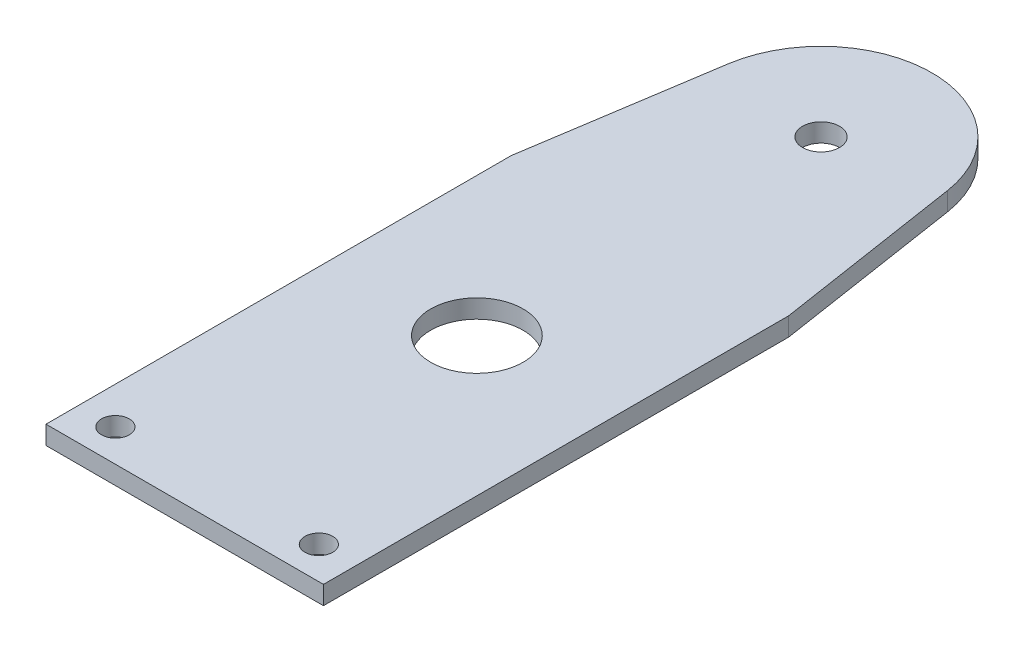
SolidWorks part; units mm, degrees
ref_plane "Спереди" through (0, 0, 0) normal (0, 0, 1) x (1, 0, 0)
ref_plane "Сверху" through (0, 0, 0) normal (0, 1, 0) x (1, 0, 0)
ref_plane "Справа" through (0, 0, 0) normal (1, 0, 0) x (0, 0, -1)
sketch "Эскиз1" plane through (0, 0, 0) normal (0, 1, 0) x (1, 0, 0)
  line L0 (-17.6252, -26.1173) -> (12.3748, -26.1173) construction
  line L1 (-17.6252, -29.6173) -> (12.3748, -29.6173) construction
  line L2 (-17.6252, -29.6173) -> (-17.6252, 48.1827) construction
  line L3 (-17.6252, 52.3827) -> (12.3748, 52.3827) construction
  line L4 (5.3748, -19.6173) -> (5.3748, -29.6173) construction
  line L5 (-13.6252, -27.6173) -> (8.3748, -27.6173) construction
  line L6 (-2.6252, -29.6173) -> (-2.6252, 60.301) construction
  line L7 (12.3748, -29.6173) -> (12.3748, 20.6827)
  line L8 (12.3748, 20.6827) -> (9.2341, 41.0146)
  line L9 (5.3748, -19.6173) -> (-10.6252, -19.6173) construction
  line L10 (5.3748, -29.6173) -> (12.3748, -29.6173)
  line L11 (-10.6252, -19.6173) -> (-10.6252, -29.6173) construction
  line L12 (-10.6252, -29.6173) -> (-17.6252, -29.6173)
  line L13 (-10.6252, -29.6173) -> (5.3748, -29.6173)
  line L14 (-17.6252, -29.6173) -> (-17.6252, 20.6827)
  line L15 (-17.6252, 20.6827) -> (-14.4846, 41.0146)
  circle A0 centre (-13.6252, -26.1173) radius 1.5
  circle A1 centre (8.3748, -26.1173) radius 1.5
  circle A2 centre (-2.6252, 39.1827) radius 2
  arc A3 (9.2341, 41.0146) -> (-14.4846, 41.0146) centre (-2.6252, 39.1827) ccw
  circle A4 centre (-2.6252, 1.9727) radius 5
  point P23 (-2.6252, -19.6173)
  dimension "D3" = 68.8
  dimension "D4" = 4
  dimension "D7" = 3
  dimension "D8" = 7
  dimension "D1" = 3.5
  dimension "D10" = 37.21
  dimension "D11" = 10
  dimension "D12" = 12
  dimension "D2" = 30
  dimension "D5" = 22
  dimension "D6" = 4
  dimension "D9" = 10
  dimension "D13" = 50.3
extrude "Бобышка-Вытянуть1" add sketch "Эскиз1" along normal blind 2
